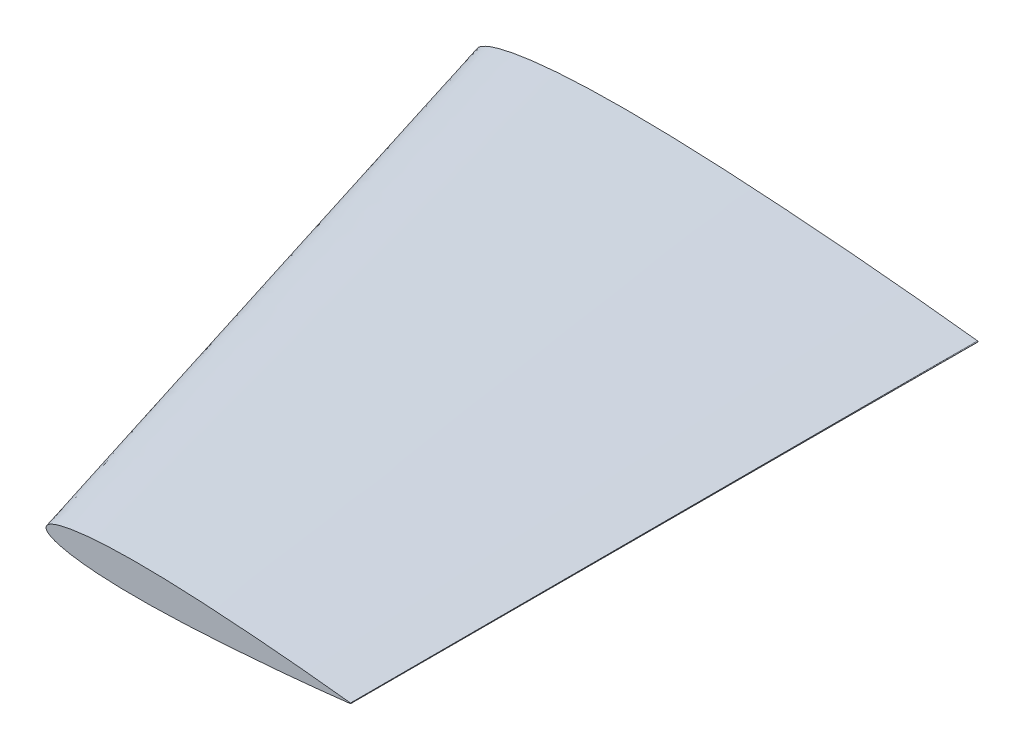
SolidWorks part; units mm, degrees
ref_plane "Front Plane" through (0, 0, 0) normal (0, 0, 1) x (1, 0, 0)
ref_plane "Top Plane" through (0, 0, 0) normal (0, 1, 0) x (1, 0, 0)
ref_plane "Right Plane" through (0, 0, 0) normal (1, 0, 0) x (0, 0, -1)
curve "Curve1"
  spline degree 3 poles (280, 0.294, 0) (279.3281, 0.3724, 0) (277.4513, 0.5912, 0) (274.0466, 0.9824, 0) (269.5431, 1.4911, 0) (264.2802, 2.073, 0) (258.4219, 2.7055, 0) (252.0786, 3.3729, 0) (245.3338, 4.0636, 0) (238.254, 4.768, 0) (230.895, 5.4785, 0) (223.3045, 6.1886, 0) (215.5245, 6.8928, 0) (207.5924, 7.586, 0) (199.5418, 8.2639, 0) (191.4036, 8.922, 0) (183.2061, 9.5566, 0) (174.9756, 10.1638, 0) (166.7367, 10.7396, 0) (158.5124, 11.2805, 0) (150.3244, 11.7828, 0) (142.1933, 12.2428, 0) (134.1386, 12.657, 0) (126.179, 13.022, 0) (118.3323, 13.3345, 0) (110.6156, 13.5915, 0) (103.0452, 13.79, 0) (95.637, 13.9275, 0) (88.4061, 14.0017, 0) (81.3674, 14.0107, 0) (74.5351, 13.9531, 0) (67.9229, 13.8279, 0) (61.5444, 13.6343, 0) (55.4124, 13.3724, 0) (49.5398, 13.0425, 0) (43.9388, 12.6455, 0) (38.6215, 12.1824, 0) (33.5995, 11.6553, 0) (28.8844, 11.066, 0) (24.4872, 10.4171, 0) (20.4189, 9.7113, 0) (16.6898, 8.9514, 0) (13.3104, 8.1407, 0) (10.2903, 7.2823, 0) (7.639, 6.3792, 0) (5.3641, 5.4342, 0) (3.475, 4.4492, 0) (1.9704, 3.4235, 0) (0.8733, 2.3505, 0) (0.1409, 1.2093, 0) (0.0454, 0.3899, 0) (0, 0, 0) knots 0 0 0 0 0.007145 0.019956 0.036196 0.055011 0.075879 0.098429 0.122376 0.147488 0.173572 0.20046 0.228005 0.256076 0.284555 0.313333 0.34231 0.371393 0.400496 0.429538 0.458442 0.487136 0.515552 0.543624 0.57129 0.598491 0.62517 0.651272 0.676746 0.701542 0.725611 0.748908 0.771388 0.793008 0.813728 0.833508 0.85231 0.870097 0.886836 0.902493 0.917037 0.930441 0.94268 0.953734 0.96359 0.972247 0.979722 0.986065 0.991385 0.995901 1 1 1 1
curve "Curve2"
  spline degree 3 poles (0, 0, 0) (0.0454, -0.3899, 0) (0.1409, -1.2093, 0) (0.8733, -2.3505, 0) (1.9704, -3.4235, 0) (3.475, -4.4492, 0) (5.3641, -5.4342, 0) (7.639, -6.3792, 0) (10.2903, -7.2823, 0) (13.3104, -8.1407, 0) (16.6898, -8.9514, 0) (20.4189, -9.7113, 0) (24.4872, -10.4171, 0) (28.8844, -11.066, 0) (33.5995, -11.6553, 0) (38.6215, -12.1824, 0) (43.9388, -12.6455, 0) (49.5398, -13.0425, 0) (55.4124, -13.3724, 0) (61.5444, -13.6343, 0) (67.9229, -13.8279, 0) (74.5351, -13.9531, 0) (81.3674, -14.0107, 0) (88.4061, -14.0017, 0) (95.637, -13.9275, 0) (103.0452, -13.79, 0) (110.6156, -13.5915, 0) (118.3323, -13.3345, 0) (126.179, -13.022, 0) (134.1386, -12.657, 0) (142.1933, -12.2428, 0) (150.3244, -11.7828, 0) (158.5124, -11.2805, 0) (166.7367, -10.7396, 0) (174.9756, -10.1638, 0) (183.2061, -9.5566, 0) (191.4036, -8.922, 0) (199.5418, -8.2639, 0) (207.5924, -7.586, 0) (215.5245, -6.8928, 0) (223.3045, -6.1886, 0) (230.895, -5.4785, 0) (238.254, -4.768, 0) (245.3338, -4.0636, 0) (252.0786, -3.3729, 0) (258.4219, -2.7055, 0) (264.2802, -2.073, 0) (269.5431, -1.4911, 0) (274.0466, -0.9824, 0) (277.4513, -0.5912, 0) (279.3281, -0.3724, 0) (280, -0.294, 0) knots 0 0 0 0 0.004099 0.008615 0.013935 0.020278 0.027753 0.03641 0.046266 0.05732 0.069559 0.082963 0.097507 0.113164 0.129903 0.14769 0.166492 0.186272 0.206992 0.228612 0.251092 0.274389 0.298458 0.323254 0.348728 0.37483 0.401509 0.42871 0.456376 0.484448 0.512864 0.541558 0.570462 0.599504 0.628607 0.65769 0.686667 0.715445 0.743924 0.771995 0.79954 0.826428 0.852512 0.877624 0.901571 0.924121 0.944989 0.963804 0.980044 0.992855 1 1 1 1
sketch "Sketch1" plane through (0, 0, 0) normal (0, 0, 1) x (1, 0, 0)
  arc A0 (280, 0.294) -> (280, -0.294) centre (280, 0) cw
  circle A1 centre (140, 0) radius 5
  circle A2 centre (70, 0) radius 5
  circle A3 centre (20, 0) radius 6
  circle A4 centre (45, 0) radius 10
  circle A5 centre (92, 0) radius 10
  circle A6 centre (119, 0) radius 10
  circle A7 centre (158, 0) radius 8.5
  circle A8 centre (180, 0) radius 6.5
  spline S0 degree 3 poles (-1914.6606, -575.7691) (64.0354, 43.2207) (-6.0406, 8.4217) (0.8733, -2.3505) (1.9704, -3.4235) (3.475, -4.4492) (5.3641, -5.4342) (7.639, -6.3792) (10.2903, -7.2823) (13.3104, -8.1407) (16.6898, -8.9514) (20.4189, -9.7113) (24.4872, -10.4171) (28.8844, -11.066) (33.5995, -11.6553) (38.6215, -12.1824) (43.9388, -12.6455) (49.5398, -13.0425) (55.4124, -13.3724) (61.5444, -13.6343) (67.9229, -13.8279) (74.5351, -13.9531) (81.3674, -14.0107) (88.4061, -14.0017) (95.637, -13.9275) (103.0452, -13.79) (110.6156, -13.5915) (118.3323, -13.3345) (126.179, -13.022) (134.1386, -12.657) (142.1933, -12.2428) (150.3244, -11.7828) (158.5124, -11.2805) (166.7367, -10.7396) (174.9756, -10.1638) (183.2061, -9.5566) (191.4036, -8.922) (199.5418, -8.2639) (207.5924, -7.586) (215.5245, -6.8928) (225.7641, -5.966) (235.7207, -5.02) (245.3338, -4.0636) (252.0786, -3.3729) (258.4219, -2.7055) (264.2802, -2.073) (269.5431, -1.4911) (274.0466, -0.9824) (390.1623, 12.3571) (503.3565, 37.5247) (844.2368, -1908.5718) knots -0.117607 -0.117607 -0.117607 -0.117607 0.004099 0.008615 0.013935 0.020278 0.027753 0.03641 0.046266 0.05732 0.069559 0.082963 0.097507 0.113164 0.129903 0.14769 0.166492 0.186272 0.206992 0.228612 0.251092 0.274389 0.298458 0.323254 0.348728 0.37483 0.401509 0.42871 0.456376 0.484448 0.512864 0.541558 0.570462 0.599504 0.628607 0.65769 0.686667 0.715445 0.743924 0.771995 0.79954 0.852512 0.877624 0.901571 0.924121 0.944989 0.963804 0.980044 0.992855 2.198236 2.198236 2.198236 2.198236 only from (0, 0) to (280, -0.294) construction
  spline S1 degree 3 poles (844.2361, 1908.5679) (503.3564, -37.5247) (390.1622, -12.3571) (274.0466, 0.9824) (269.5431, 1.4911) (264.2802, 2.073) (258.4219, 2.7055) (252.0786, 3.3729) (245.3338, 4.0636) (235.7207, 5.02) (225.7641, 5.966) (215.5245, 6.8928) (207.5924, 7.586) (199.5418, 8.2639) (191.4036, 8.922) (183.2061, 9.5566) (174.9756, 10.1638) (166.7367, 10.7396) (158.5124, 11.2805) (150.3244, 11.7828) (142.1933, 12.2428) (134.1386, 12.657) (126.179, 13.022) (118.3323, 13.3345) (110.6156, 13.5915) (103.0452, 13.79) (95.637, 13.9275) (88.4061, 14.0017) (81.3674, 14.0107) (74.5351, 13.9531) (67.9229, 13.8279) (61.5444, 13.6343) (55.4124, 13.3724) (49.5398, 13.0425) (43.9388, 12.6455) (38.6215, 12.1824) (33.5995, 11.6553) (28.8844, 11.066) (24.4872, 10.4171) (20.4189, 9.7113) (16.6898, 8.9514) (13.3104, 8.1407) (10.2903, 7.2823) (7.639, 6.3792) (5.3641, 5.4342) (3.475, 4.4492) (1.9704, 3.4235) (0.8733, 2.3505) (-6.0403, -8.4213) (64.03, -43.218) (-1914.4229, 575.6948) knots -1.198235 -1.198235 -1.198235 -1.198235 0.007145 0.019956 0.036196 0.055011 0.075879 0.098429 0.122376 0.147488 0.20046 0.228005 0.256076 0.284555 0.313333 0.34231 0.371393 0.400496 0.429538 0.458442 0.487136 0.515552 0.543624 0.57129 0.598491 0.62517 0.651272 0.676746 0.701542 0.725611 0.748908 0.771388 0.793008 0.813728 0.833508 0.85231 0.870097 0.886836 0.902493 0.917037 0.930441 0.94268 0.953734 0.96359 0.972247 0.979722 0.986065 0.991385 0.995901 1.117602 1.117602 1.117602 1.117602 only from (280, 0.294) to (0, 0) construction
  spline S2 degree 3 poles (0, 0) (0.0454, -0.3899) (0.1409, -1.2093) (0.8733, -2.3505) (1.9704, -3.4235) (3.475, -4.4492) (5.3641, -5.4342) (7.639, -6.3792) (10.2903, -7.2823) (13.3104, -8.1407) (16.6898, -8.9514) (20.4189, -9.7113) (24.4872, -10.4171) (28.8844, -11.066) (33.5995, -11.6553) (38.6215, -12.1824) (43.9388, -12.6455) (49.5398, -13.0425) (55.4124, -13.3724) (61.5444, -13.6343) (67.9229, -13.8279) (74.5351, -13.9531) (81.3674, -14.0107) (88.4061, -14.0017) (95.637, -13.9275) (103.0452, -13.79) (110.6156, -13.5915) (118.3323, -13.3345) (126.179, -13.022) (134.1386, -12.657) (142.1933, -12.2428) (150.3244, -11.7828) (158.5124, -11.2805) (166.7367, -10.7396) (174.9756, -10.1638) (183.2061, -9.5566) (191.4036, -8.922) (199.5418, -8.2639) (207.5924, -7.586) (215.5245, -6.8928) (225.7641, -5.966) (235.7207, -5.02) (245.3338, -4.0636) (252.0786, -3.3729) (258.4219, -2.7055) (264.2802, -2.073) (269.5431, -1.4911) (274.0466, -0.9824) (277.4513, -0.5912) (279.3281, -0.3724) (280, -0.294) knots 0 0 0 0 0.004099 0.008615 0.013935 0.020278 0.027753 0.03641 0.046266 0.05732 0.069559 0.082963 0.097507 0.113164 0.129903 0.14769 0.166492 0.186272 0.206992 0.228612 0.251092 0.274389 0.298458 0.323254 0.348728 0.37483 0.401509 0.42871 0.456376 0.484448 0.512864 0.541558 0.570462 0.599504 0.628607 0.65769 0.686667 0.715445 0.743924 0.771995 0.79954 0.852512 0.877624 0.901571 0.924121 0.944989 0.963804 0.980044 0.992855 1 1 1 1
  spline S3 degree 3 poles (280, 0.294) (279.3281, 0.3724) (277.4513, 0.5912) (274.0466, 0.9824) (269.5431, 1.4911) (264.2802, 2.073) (258.4219, 2.7055) (252.0786, 3.3729) (245.3338, 4.0636) (235.7207, 5.02) (225.7641, 5.966) (215.5245, 6.8928) (207.5924, 7.586) (199.5418, 8.2639) (191.4036, 8.922) (183.2061, 9.5566) (174.9756, 10.1638) (166.7367, 10.7396) (158.5124, 11.2805) (150.3244, 11.7828) (142.1933, 12.2428) (134.1386, 12.657) (126.179, 13.022) (118.3323, 13.3345) (110.6156, 13.5915) (103.0452, 13.79) (95.637, 13.9275) (88.4061, 14.0017) (81.3674, 14.0107) (74.5351, 13.9531) (67.9229, 13.8279) (61.5444, 13.6343) (55.4124, 13.3724) (49.5398, 13.0425) (43.9388, 12.6455) (38.6215, 12.1824) (33.5995, 11.6553) (28.8844, 11.066) (24.4872, 10.4171) (20.4189, 9.7113) (16.6898, 8.9514) (13.3104, 8.1407) (10.2903, 7.2823) (7.639, 6.3792) (5.3641, 5.4342) (3.475, 4.4492) (1.9704, 3.4235) (0.8733, 2.3505) (0.1409, 1.2093) (0.0454, 0.3899) (0, 0) knots 0 0 0 0 0.007145 0.019956 0.036196 0.055011 0.075879 0.098429 0.122376 0.147488 0.20046 0.228005 0.256076 0.284555 0.313333 0.34231 0.371393 0.400496 0.429538 0.458442 0.487136 0.515552 0.543624 0.57129 0.598491 0.62517 0.651272 0.676746 0.701542 0.725611 0.748908 0.771388 0.793008 0.813728 0.833508 0.85231 0.870097 0.886836 0.902493 0.917037 0.930441 0.94268 0.953734 0.96359 0.972247 0.979722 0.986065 0.991385 0.995901 1 1 1 1
  dimension "D1" = 0.294
  dimension "D3" = 10
  dimension "D5" = 10
  dimension "D6" = 20
  dimension "D7" = 12
  dimension "D8" = 20
  dimension "D9" = 20
  dimension "D10" = 17
  dimension "D11" = 13
  dimension "D2" = 140
  dimension "D4" = 70
  dimension "D12" = 20
  dimension "D13" = 45
  dimension "D14" = 92
  dimension "D15" = 119
  dimension "D16" = 158
  dimension "D17" = 180
ref_plane "Plane4" through (0, 0, 175) normal (0, 0, 1) x (1, 0, 0)
ref_plane "Plane5" through (0, 0, 350) normal (0, 0, 1) x (1, 0, 0)
curve "Кривая1"
  spline degree 3 poles (280, 0.2362, 0) (279.4601, 0.2992, 0) (277.952, 0.4751, 0) (275.216, 0.7894, 0) (271.5971, 1.1982, 0) (267.368, 1.6658, 0) (262.6604, 2.174, 0) (257.5632, 2.7104, 0) (252.1432, 3.2654, 0) (246.4541, 3.8314, 0) (240.5406, 4.4024, 0) (234.4411, 4.973, 0) (228.1894, 5.5389, 0) (221.8153, 6.0959, 0) (215.3461, 6.6406, 0) (208.8064, 7.1695, 0) (202.2192, 7.6794, 0) (195.6054, 8.1673, 0) (188.9848, 8.63, 0) (182.376, 9.0647, 0) (175.7964, 9.4683, 0) (169.2625, 9.8379, 0) (162.79, 10.1708, 0) (156.3939, 10.4641, 0) (150.0885, 10.7152, 0) (143.8875, 10.9217, 0) (137.8042, 11.0812, 0) (131.8511, 11.1917, 0) (126.0406, 11.2513, 0) (120.3845, 11.2586, 0) (114.8943, 11.2123, 0) (109.5809, 11.1117, 0) (104.4553, 10.9562, 0) (99.5279, 10.7457, 0) (94.8088, 10.4806, 0) (90.308, 10.1615, 0) (86.0351, 9.7895, 0) (81.9996, 9.3659, 0) (78.2107, 8.8923, 0) (74.6772, 8.3709, 0) (71.408, 7.8037, 0) (68.4115, 7.1931, 0) (65.6959, 6.5416, 0) (63.269, 5.8518, 0) (61.1384, 5.1261, 0) (59.3105, 4.3667, 0) (57.7924, 3.5753, 0) (56.5834, 2.751, 0) (55.7018, 1.8888, 0) (55.1132, 0.9718, 0) (55.0365, 0.3133, 0) (55, 0, 0) knots 0 0 0 0 0.007145 0.019956 0.036196 0.055011 0.075879 0.098429 0.122376 0.147488 0.173572 0.20046 0.228005 0.256076 0.284555 0.313333 0.34231 0.371393 0.400496 0.429538 0.458442 0.487136 0.515552 0.543624 0.57129 0.598491 0.62517 0.651272 0.676746 0.701542 0.725611 0.748908 0.771388 0.793008 0.813728 0.833508 0.85231 0.870097 0.886836 0.902493 0.917037 0.930441 0.94268 0.953734 0.96359 0.972247 0.979722 0.986065 0.991385 0.995901 1 1 1 1
curve "Кривая2"
  spline degree 3 poles (55, 0, 0) (55.0365, -0.3133, 0) (55.1132, -0.9718, 0) (55.7018, -1.8888, 0) (56.5834, -2.751, 0) (57.7924, -3.5753, 0) (59.3105, -4.3667, 0) (61.1384, -5.1261, 0) (63.269, -5.8518, 0) (65.6959, -6.5416, 0) (68.4115, -7.1931, 0) (71.408, -7.8037, 0) (74.6772, -8.3709, 0) (78.2107, -8.8923, 0) (81.9996, -9.3659, 0) (86.0351, -9.7895, 0) (90.308, -10.1615, 0) (94.8088, -10.4806, 0) (99.5279, -10.7457, 0) (104.4553, -10.9562, 0) (109.5809, -11.1117, 0) (114.8943, -11.2123, 0) (120.3845, -11.2586, 0) (126.0406, -11.2513, 0) (131.8511, -11.1917, 0) (137.8042, -11.0812, 0) (143.8875, -10.9217, 0) (150.0885, -10.7152, 0) (156.3939, -10.4641, 0) (162.79, -10.1708, 0) (169.2625, -9.8379, 0) (175.7964, -9.4683, 0) (182.376, -9.0647, 0) (188.9848, -8.63, 0) (195.6054, -8.1673, 0) (202.2192, -7.6794, 0) (208.8064, -7.1695, 0) (215.3461, -6.6406, 0) (221.8153, -6.0959, 0) (228.1894, -5.5389, 0) (234.4411, -4.973, 0) (240.5406, -4.4024, 0) (246.4541, -3.8314, 0) (252.1432, -3.2654, 0) (257.5632, -2.7104, 0) (262.6604, -2.174, 0) (267.368, -1.6658, 0) (271.5971, -1.1982, 0) (275.216, -0.7894, 0) (277.952, -0.4751, 0) (279.4601, -0.2992, 0) (280, -0.2362, 0) knots 0 0 0 0 0.004099 0.008615 0.013935 0.020278 0.027753 0.03641 0.046266 0.05732 0.069559 0.082963 0.097507 0.113164 0.129903 0.14769 0.166492 0.186272 0.206992 0.228612 0.251092 0.274389 0.298458 0.323254 0.348728 0.37483 0.401509 0.42871 0.456376 0.484448 0.512864 0.541558 0.570462 0.599504 0.628607 0.65769 0.686667 0.715445 0.743924 0.771995 0.79954 0.826428 0.852512 0.877624 0.901571 0.924121 0.944989 0.963804 0.980044 0.992855 1 1 1 1
sketch "Эскиз1" plane through (0, 0, 175) normal (0, 0, 1) x (1, 0, 0)
  line L0 (280, 0.2362) -> (280, -0.2362)
  circle A0 centre (140, 0) radius 5
  circle A1 centre (70, 0) radius 5
  circle A2 centre (91, 0) radius 7.5
  circle A3 centre (115, 0) radius 9
  circle A4 centre (160, 0) radius 7.5
  circle A5 centre (180, 0) radius 6
  circle A6 centre (200, 0) radius 5
  spline S0 degree 3 poles (-2811.7718, -879.7739) (133.5287, 47.6678) (48.9994, 8.5537) (55.7018, -1.8888) (56.5834, -2.751) (57.7924, -3.5753) (59.3105, -4.3667) (61.1384, -5.1261) (63.269, -5.8518) (65.6959, -6.5416) (68.4115, -7.1931) (71.408, -7.8037) (74.6772, -8.3709) (78.2107, -8.8923) (81.9996, -9.3659) (86.0351, -9.7895) (90.308, -10.1615) (94.8088, -10.4806) (99.5279, -10.7457) (104.4553, -10.9562) (109.5809, -11.1117) (114.8943, -11.2123) (120.3845, -11.2586) (126.0406, -11.2513) (131.8511, -11.1917) (137.8042, -11.0812) (143.8875, -10.9217) (150.0885, -10.7152) (156.3939, -10.4641) (162.79, -10.1708) (169.2625, -9.8379) (175.7964, -9.4683) (182.376, -9.0647) (188.9848, -8.63) (195.6054, -8.1673) (202.2192, -7.6794) (208.8064, -7.1695) (215.3461, -6.6406) (221.8153, -6.0959) (228.1894, -5.5389) (236.4176, -4.7941) (244.4184, -4.0339) (252.1432, -3.2654) (257.5632, -2.7104) (262.6604, -2.174) (267.368, -1.6658) (271.5971, -1.1982) (275.216, -0.7894) (389.8301, 12.3776) (501.5182, 40.0297) (958.1183, -2911.0244) knots -0.144752 -0.144752 -0.144752 -0.144752 0.004099 0.008615 0.013935 0.020278 0.027753 0.03641 0.046266 0.05732 0.069559 0.082963 0.097507 0.113164 0.129903 0.14769 0.166492 0.186272 0.206992 0.228612 0.251092 0.274389 0.298458 0.323254 0.348728 0.37483 0.401509 0.42871 0.456376 0.484448 0.512864 0.541558 0.570462 0.599504 0.628607 0.65769 0.686667 0.715445 0.743924 0.771995 0.79954 0.852512 0.877624 0.901571 0.924121 0.944989 0.963804 0.980044 0.992855 2.48012 2.48012 2.48012 2.48012 only from (55, 0) to (280, -0.2362) construction
  spline S1 degree 3 poles (958.116, 2911.0096) (501.5178, -40.0296) (389.8299, -12.3775) (275.216, 0.7894) (271.5971, 1.1982) (267.368, 1.6658) (262.6604, 2.174) (257.5632, 2.7104) (252.1432, 3.2654) (244.4184, 4.0339) (236.4176, 4.7941) (228.1894, 5.5389) (221.8153, 6.0959) (215.3461, 6.6406) (208.8064, 7.1695) (202.2192, 7.6794) (195.6054, 8.1673) (188.9848, 8.63) (182.376, 9.0647) (175.7964, 9.4683) (169.2625, 9.8379) (162.79, 10.1708) (156.3939, 10.4641) (150.0885, 10.7152) (143.8875, 10.9217) (137.8042, 11.0812) (131.8511, 11.1917) (126.0406, 11.2513) (120.3845, 11.2586) (114.8943, 11.2123) (109.5809, 11.1117) (104.4553, 10.9562) (99.5279, 10.7457) (94.8088, 10.4806) (90.308, 10.1615) (86.0351, 9.7895) (81.9996, 9.3659) (78.2107, 8.8923) (74.6772, 8.3709) (71.408, 7.8037) (68.4115, 7.1931) (65.6959, 6.5416) (63.269, 5.8518) (61.1384, 5.1261) (59.3105, 4.3667) (57.7924, 3.5753) (56.5834, 2.751) (55.7018, 1.8888) (48.9996, -8.5535) (133.5252, -47.6662) (-2811.5821, 879.7142) knots -1.480117 -1.480117 -1.480117 -1.480117 0.007145 0.019956 0.036196 0.055011 0.075879 0.098429 0.122376 0.147488 0.20046 0.228005 0.256076 0.284555 0.313333 0.34231 0.371393 0.400496 0.429538 0.458442 0.487136 0.515552 0.543624 0.57129 0.598491 0.62517 0.651272 0.676746 0.701542 0.725611 0.748908 0.771388 0.793008 0.813728 0.833508 0.85231 0.870097 0.886836 0.902493 0.917037 0.930441 0.94268 0.953734 0.96359 0.972247 0.979722 0.986065 0.991385 0.995901 1.144749 1.144749 1.144749 1.144749 only from (280, 0.2362) to (55, 0) construction
  spline S2 degree 3 poles (55, 0) (55.0365, -0.3133) (55.1132, -0.9718) (55.7018, -1.8888) (56.5834, -2.751) (57.7924, -3.5753) (59.3105, -4.3667) (61.1384, -5.1261) (63.269, -5.8518) (65.6959, -6.5416) (68.4115, -7.1931) (71.408, -7.8037) (74.6772, -8.3709) (78.2107, -8.8923) (81.9996, -9.3659) (86.0351, -9.7895) (90.308, -10.1615) (94.8088, -10.4806) (99.5279, -10.7457) (104.4553, -10.9562) (109.5809, -11.1117) (114.8943, -11.2123) (120.3845, -11.2586) (126.0406, -11.2513) (131.8511, -11.1917) (137.8042, -11.0812) (143.8875, -10.9217) (150.0885, -10.7152) (156.3939, -10.4641) (162.79, -10.1708) (169.2625, -9.8379) (175.7964, -9.4683) (182.376, -9.0647) (188.9848, -8.63) (195.6054, -8.1673) (202.2192, -7.6794) (208.8064, -7.1695) (215.3461, -6.6406) (221.8153, -6.0959) (228.1894, -5.5389) (236.4176, -4.7941) (244.4184, -4.0339) (252.1432, -3.2654) (257.5632, -2.7104) (262.6604, -2.174) (267.368, -1.6658) (271.5971, -1.1982) (275.216, -0.7894) (277.952, -0.4751) (279.4601, -0.2992) (280, -0.2362) knots 0 0 0 0 0.004099 0.008615 0.013935 0.020278 0.027753 0.03641 0.046266 0.05732 0.069559 0.082963 0.097507 0.113164 0.129903 0.14769 0.166492 0.186272 0.206992 0.228612 0.251092 0.274389 0.298458 0.323254 0.348728 0.37483 0.401509 0.42871 0.456376 0.484448 0.512864 0.541558 0.570462 0.599504 0.628607 0.65769 0.686667 0.715445 0.743924 0.771995 0.79954 0.852512 0.877624 0.901571 0.924121 0.944989 0.963804 0.980044 0.992855 1 1 1 1
  spline S3 degree 3 poles (280, 0.2362) (279.4601, 0.2992) (277.952, 0.4751) (275.216, 0.7894) (271.5971, 1.1982) (267.368, 1.6658) (262.6604, 2.174) (257.5632, 2.7104) (252.1432, 3.2654) (244.4184, 4.0339) (236.4176, 4.7941) (228.1894, 5.5389) (221.8153, 6.0959) (215.3461, 6.6406) (208.8064, 7.1695) (202.2192, 7.6794) (195.6054, 8.1673) (188.9848, 8.63) (182.376, 9.0647) (175.7964, 9.4683) (169.2625, 9.8379) (162.79, 10.1708) (156.3939, 10.4641) (150.0885, 10.7152) (143.8875, 10.9217) (137.8042, 11.0812) (131.8511, 11.1917) (126.0406, 11.2513) (120.3845, 11.2586) (114.8943, 11.2123) (109.5809, 11.1117) (104.4553, 10.9562) (99.5279, 10.7457) (94.8088, 10.4806) (90.308, 10.1615) (86.0351, 9.7895) (81.9996, 9.3659) (78.2107, 8.8923) (74.6772, 8.3709) (71.408, 7.8037) (68.4115, 7.1931) (65.6959, 6.5416) (63.269, 5.8518) (61.1384, 5.1261) (59.3105, 4.3667) (57.7924, 3.5753) (56.5834, 2.751) (55.7018, 1.8888) (55.1132, 0.9718) (55.0365, 0.3133) (55, 0) knots 0 0 0 0 0.007145 0.019956 0.036196 0.055011 0.075879 0.098429 0.122376 0.147488 0.20046 0.228005 0.256076 0.284555 0.313333 0.34231 0.371393 0.400496 0.429538 0.458442 0.487136 0.515552 0.543624 0.57129 0.598491 0.62517 0.651272 0.676746 0.701542 0.725611 0.748908 0.771388 0.793008 0.813728 0.833508 0.85231 0.870097 0.886836 0.902493 0.917037 0.930441 0.94268 0.953734 0.96359 0.972247 0.979722 0.986065 0.991385 0.995901 1 1 1 1
  point P17 (115.888, 0)
  point P18 (91.8201, 0)
  dimension "D1" = 10
  dimension "D3" = 10
  dimension "D5" = 15
  dimension "D6" = 18
  dimension "D7" = 15
  dimension "D8" = 12
  dimension "D9" = 10
  dimension "D2" = 85
  dimension "D4" = 15
  dimension "D10" = 36
  dimension "D11" = 60
  dimension "D12" = 105
  dimension "D13" = 125
  dimension "D14" = 145
curve "Кривая3"
  spline degree 3 poles (280, 0.1785, 0) (279.592, 0.2261, 0) (278.4526, 0.359, 0) (276.3854, 0.5964, 0) (273.6512, 0.9053, 0) (270.4558, 1.2586, 0) (266.899, 1.6426, 0) (263.0477, 2.0479, 0) (258.9526, 2.4672, 0) (254.6542, 2.8948, 0) (250.1862, 3.3262, 0) (245.5777, 3.7574, 0) (240.8542, 4.1849, 0) (236.0382, 4.6058, 0) (231.1504, 5.0174, 0) (226.2093, 5.417, 0) (221.2323, 5.8022, 0) (216.2352, 6.1709, 0) (211.233, 6.5205, 0) (206.2396, 6.8489, 0) (201.2684, 7.1538, 0) (196.3316, 7.4331, 0) (191.4413, 7.6846, 0) (186.6087, 7.9062, 0) (181.8446, 8.096, 0) (177.1595, 8.252, 0) (172.5632, 8.3725, 0) (168.0653, 8.456, 0) (163.6751, 8.501, 0) (159.4016, 8.5065, 0) (155.2534, 8.4715, 0) (151.2389, 8.3955, 0) (147.3662, 8.278, 0) (143.6433, 8.119, 0) (140.0777, 7.9187, 0) (136.6771, 7.6776, 0) (133.4488, 7.3965, 0) (130.3997, 7.0764, 0) (127.537, 6.7187, 0) (124.8672, 6.3247, 0) (122.3972, 5.8961, 0) (120.1331, 5.4348, 0) (118.0813, 4.9426, 0) (116.2477, 4.4214, 0) (114.6379, 3.8731, 0) (113.2568, 3.2993, 0) (112.1098, 2.7013, 0) (111.1963, 2.0786, 0) (110.5302, 1.4271, 0) (110.0855, 0.7342, 0) (110.0276, 0.2367, 0) (110, 0, 0) knots 0 0 0 0 0.007145 0.019956 0.036196 0.055011 0.075879 0.098429 0.122376 0.147488 0.173572 0.20046 0.228005 0.256076 0.284555 0.313333 0.34231 0.371393 0.400496 0.429538 0.458442 0.487136 0.515552 0.543624 0.57129 0.598491 0.62517 0.651272 0.676746 0.701542 0.725611 0.748908 0.771388 0.793008 0.813728 0.833508 0.85231 0.870097 0.886836 0.902493 0.917037 0.930441 0.94268 0.953734 0.96359 0.972247 0.979722 0.986065 0.991385 0.995901 1 1 1 1
curve "Кривая4"
  spline degree 3 poles (110, 0, 0) (110.0276, -0.2367, 0) (110.0855, -0.7342, 0) (110.5302, -1.4271, 0) (111.1963, -2.0786, 0) (112.1098, -2.7013, 0) (113.2568, -3.2993, 0) (114.6379, -3.8731, 0) (116.2477, -4.4214, 0) (118.0813, -4.9426, 0) (120.1331, -5.4348, 0) (122.3972, -5.8961, 0) (124.8672, -6.3247, 0) (127.537, -6.7187, 0) (130.3997, -7.0764, 0) (133.4488, -7.3965, 0) (136.6771, -7.6776, 0) (140.0777, -7.9187, 0) (143.6433, -8.119, 0) (147.3662, -8.278, 0) (151.2389, -8.3955, 0) (155.2534, -8.4715, 0) (159.4016, -8.5065, 0) (163.6751, -8.501, 0) (168.0653, -8.456, 0) (172.5632, -8.3725, 0) (177.1595, -8.252, 0) (181.8446, -8.096, 0) (186.6087, -7.9062, 0) (191.4413, -7.6846, 0) (196.3316, -7.4331, 0) (201.2684, -7.1538, 0) (206.2396, -6.8489, 0) (211.233, -6.5205, 0) (216.2352, -6.1709, 0) (221.2323, -5.8022, 0) (226.2093, -5.417, 0) (231.1504, -5.0174, 0) (236.0382, -4.6058, 0) (240.8542, -4.1849, 0) (245.5777, -3.7574, 0) (250.1862, -3.3262, 0) (254.6542, -2.8948, 0) (258.9526, -2.4672, 0) (263.0477, -2.0479, 0) (266.899, -1.6426, 0) (270.4558, -1.2586, 0) (273.6512, -0.9053, 0) (276.3854, -0.5964, 0) (278.4526, -0.359, 0) (279.592, -0.2261, 0) (280, -0.1785, 0) knots 0 0 0 0 0.004099 0.008615 0.013935 0.020278 0.027753 0.03641 0.046266 0.05732 0.069559 0.082963 0.097507 0.113164 0.129903 0.14769 0.166492 0.186272 0.206992 0.228612 0.251092 0.274389 0.298458 0.323254 0.348728 0.37483 0.401509 0.42871 0.456376 0.484448 0.512864 0.541558 0.570462 0.599504 0.628607 0.65769 0.686667 0.715445 0.743924 0.771995 0.79954 0.826428 0.852512 0.877624 0.901571 0.924121 0.944989 0.963804 0.980044 0.992855 1 1 1 1
sketch "Эскиз2" plane through (0, 0, 350) normal (0, 0, 1) x (1, 0, 0)
  line L0 (280, 0.1785) -> (280, -0.1785)
  circle A2 centre (140, 0) radius 5
  spline S0 degree 3 poles (751.5383, 1938.3796) (440.561, -28.5775) (359.5279, -8.955) (276.3854, 0.5964) (273.6512, 0.9053) (270.4558, 1.2586) (266.899, 1.6426) (263.0477, 2.0479) (258.9526, 2.4672) (253.1161, 3.0479) (247.0711, 3.6222) (240.8542, 4.1849) (236.0382, 4.6058) (231.1504, 5.0174) (226.2093, 5.417) (221.2323, 5.8022) (216.2352, 6.1709) (211.233, 6.5205) (206.2396, 6.8489) (201.2684, 7.1538) (196.3316, 7.4331) (191.4413, 7.6846) (186.6087, 7.9062) (181.8446, 8.096) (177.1595, 8.252) (172.5632, 8.3725) (168.0653, 8.456) (163.6751, 8.501) (159.4016, 8.5065) (155.2534, 8.4715) (151.2389, 8.3955) (147.3662, 8.278) (143.6433, 8.119) (140.0777, 7.9187) (136.6771, 7.6776) (133.4488, 7.3965) (130.3997, 7.0764) (127.537, 6.7187) (124.8672, 6.3247) (122.3972, 5.8961) (120.1331, 5.4348) (118.0813, 4.9426) (116.2477, 4.4214) (114.6379, 3.8731) (113.2568, 3.2993) (112.1098, 2.7013) (111.1963, 2.0786) (110.5302, 1.4271) (105.6546, -6.1694) (164.5198, -33.7739) (-1801.974, 584.7691) knots -1.419625 -1.419625 -1.419625 -1.419625 0.007145 0.019956 0.036196 0.055011 0.075879 0.098429 0.122376 0.147488 0.20046 0.228005 0.256076 0.284555 0.313333 0.34231 0.371393 0.400496 0.429538 0.458442 0.487136 0.515552 0.543624 0.57129 0.598491 0.62517 0.651272 0.676746 0.701542 0.725611 0.748908 0.771388 0.793008 0.813728 0.833508 0.85231 0.870097 0.886836 0.902493 0.917037 0.930441 0.94268 0.953734 0.96359 0.972247 0.979722 0.986065 0.991385 0.995901 1.138851 1.138851 1.138851 1.138851 only from (280, 0.1785) to (110, 0) construction
  spline S1 degree 3 poles (-1802.3351, -584.8827) (164.5267, 33.7772) (105.6543, 6.1699) (110.5302, -1.4271) (111.1963, -2.0786) (112.1098, -2.7013) (113.2568, -3.2993) (114.6379, -3.8731) (116.2477, -4.4214) (118.0813, -4.9426) (120.1331, -5.4348) (122.3972, -5.8961) (124.8672, -6.3247) (127.537, -6.7187) (130.3997, -7.0764) (133.4488, -7.3965) (136.6771, -7.6776) (140.0777, -7.9187) (143.6433, -8.119) (147.3662, -8.278) (151.2389, -8.3955) (155.2534, -8.4715) (159.4016, -8.5065) (163.6751, -8.501) (168.0653, -8.456) (172.5632, -8.3725) (177.1595, -8.252) (181.8446, -8.096) (186.6087, -7.9062) (191.4413, -7.6846) (196.3316, -7.4331) (201.2684, -7.1538) (206.2396, -6.8489) (211.233, -6.5205) (216.2352, -6.1709) (221.2323, -5.8022) (226.2093, -5.417) (231.1504, -5.0174) (236.0382, -4.6058) (240.8542, -4.1849) (247.0711, -3.6222) (253.1161, -3.0479) (258.9526, -2.4672) (263.0477, -2.0479) (266.899, -1.6426) (270.4558, -1.2586) (273.6512, -0.9053) (276.3854, -0.5964) (359.5279, 8.955) (440.5611, 28.5776) (751.5392, -1938.3855) knots -0.13886 -0.13886 -0.13886 -0.13886 0.004099 0.008615 0.013935 0.020278 0.027753 0.03641 0.046266 0.05732 0.069559 0.082963 0.097507 0.113164 0.129903 0.14769 0.166492 0.186272 0.206992 0.228612 0.251092 0.274389 0.298458 0.323254 0.348728 0.37483 0.401509 0.42871 0.456376 0.484448 0.512864 0.541558 0.570462 0.599504 0.628607 0.65769 0.686667 0.715445 0.743924 0.771995 0.79954 0.852512 0.877624 0.901571 0.924121 0.944989 0.963804 0.980044 0.992855 2.419626 2.419626 2.419626 2.419626 only from (110, 0) to (280, -0.1785) construction
  spline S2 degree 3 poles (280, 0.1785) (279.592, 0.2261) (278.4526, 0.359) (276.3854, 0.5964) (273.6512, 0.9053) (270.4558, 1.2586) (266.899, 1.6426) (263.0477, 2.0479) (258.9526, 2.4672) (253.1161, 3.0479) (247.0711, 3.6222) (240.8542, 4.1849) (236.0382, 4.6058) (231.1504, 5.0174) (226.2093, 5.417) (221.2323, 5.8022) (216.2352, 6.1709) (211.233, 6.5205) (206.2396, 6.8489) (201.2684, 7.1538) (196.3316, 7.4331) (191.4413, 7.6846) (186.6087, 7.9062) (181.8446, 8.096) (177.1595, 8.252) (172.5632, 8.3725) (168.0653, 8.456) (163.6751, 8.501) (159.4016, 8.5065) (155.2534, 8.4715) (151.2389, 8.3955) (147.3662, 8.278) (143.6433, 8.119) (140.0777, 7.9187) (136.6771, 7.6776) (133.4488, 7.3965) (130.3997, 7.0764) (127.537, 6.7187) (124.8672, 6.3247) (122.3972, 5.8961) (120.1331, 5.4348) (118.0813, 4.9426) (116.2477, 4.4214) (114.6379, 3.8731) (113.2568, 3.2993) (112.1098, 2.7013) (111.1963, 2.0786) (110.5302, 1.4271) (110.0855, 0.7342) (110.0276, 0.2367) (110, 0) knots 0 0 0 0 0.007145 0.019956 0.036196 0.055011 0.075879 0.098429 0.122376 0.147488 0.20046 0.228005 0.256076 0.284555 0.313333 0.34231 0.371393 0.400496 0.429538 0.458442 0.487136 0.515552 0.543624 0.57129 0.598491 0.62517 0.651272 0.676746 0.701542 0.725611 0.748908 0.771388 0.793008 0.813728 0.833508 0.85231 0.870097 0.886836 0.902493 0.917037 0.930441 0.94268 0.953734 0.96359 0.972247 0.979722 0.986065 0.991385 0.995901 1 1 1 1
  spline S3 degree 3 poles (110, 0) (110.0276, -0.2367) (110.0855, -0.7342) (110.5302, -1.4271) (111.1963, -2.0786) (112.1098, -2.7013) (113.2568, -3.2993) (114.6379, -3.8731) (116.2477, -4.4214) (118.0813, -4.9426) (120.1331, -5.4348) (122.3972, -5.8961) (124.8672, -6.3247) (127.537, -6.7187) (130.3997, -7.0764) (133.4488, -7.3965) (136.6771, -7.6776) (140.0777, -7.9187) (143.6433, -8.119) (147.3662, -8.278) (151.2389, -8.3955) (155.2534, -8.4715) (159.4016, -8.5065) (163.6751, -8.501) (168.0653, -8.456) (172.5632, -8.3725) (177.1595, -8.252) (181.8446, -8.096) (186.6087, -7.9062) (191.4413, -7.6846) (196.3316, -7.4331) (201.2684, -7.1538) (206.2396, -6.8489) (211.233, -6.5205) (216.2352, -6.1709) (221.2323, -5.8022) (226.2093, -5.417) (231.1504, -5.0174) (236.0382, -4.6058) (240.8542, -4.1849) (247.0711, -3.6222) (253.1161, -3.0479) (258.9526, -2.4672) (263.0477, -2.0479) (266.899, -1.6426) (270.4558, -1.2586) (273.6512, -0.9053) (276.3854, -0.5964) (278.4526, -0.359) (279.592, -0.2261) (280, -0.1785) knots 0 0 0 0 0.004099 0.008615 0.013935 0.020278 0.027753 0.03641 0.046266 0.05732 0.069559 0.082963 0.097507 0.113164 0.129903 0.14769 0.166492 0.186272 0.206992 0.228612 0.251092 0.274389 0.298458 0.323254 0.348728 0.37483 0.401509 0.42871 0.456376 0.484448 0.512864 0.541558 0.570462 0.599504 0.628607 0.65769 0.686667 0.715445 0.743924 0.771995 0.79954 0.852512 0.877624 0.901571 0.924121 0.944989 0.963804 0.980044 0.992855 1 1 1 1
  dimension "D1" = 10
  dimension "D2" = 30
loft "По сечениям3" add section "Sketch1" section "Эскиз1" section "Эскиз2" start constraint default end constraint default connector at (0, 0, 0) connector at (55, 0, 175) connector at (110, 0, 350)
